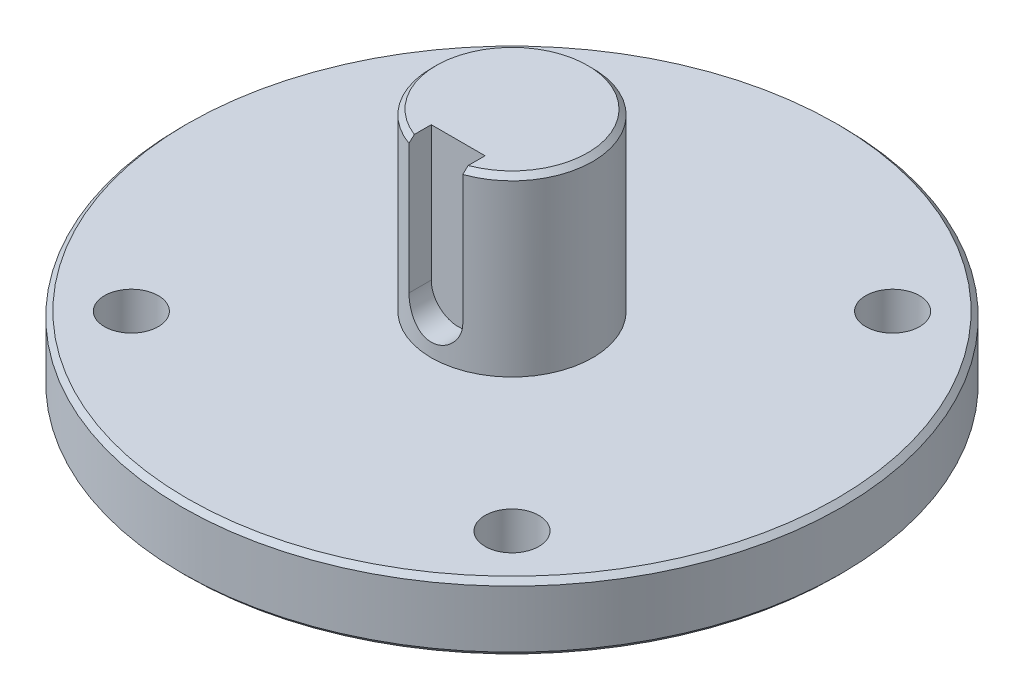
SolidWorks part; units mm, degrees
material "AISI 1045 Steel, cold drawn"
ref_plane "Front Plane" through (0, 0, 0) normal (0, 0, 1) x (1, 0, 0)
ref_plane "Top Plane" through (0, 0, 0) normal (0, 1, 0) x (1, 0, 0)
ref_plane "Right Plane" through (0, 0, 0) normal (1, 0, 0) x (0, 0, -1)
sketch "Sketch1" plane through (0, 0, 0) normal (0, 0, 1) x (1, 0, 0)
  line L0 (0, 0) -> (-49, 0)
  line L1 (-49, 0) -> (-49, 10)
  line L2 (-49, 10) -> (-12, 10)
  line L3 (-12, 10) -> (-12, 36)
  line L4 (-12, 36) -> (0, 36)
  line L5 (0, 36) -> (0, 0)
  dimension "D1" = 12
  dimension "D2" = 26
  dimension "D3" = 10
  dimension "D4" = 49
revolve "Revolve1" add sketch "Sketch1" angle 360 about L5
sketch "Sketch2" plane through (0, 10, 0) normal (0, 1, 0) x (1, 0, 0)
  line L1 (-28.2843, -28.2843) -> (28.2843, -28.2843) construction
  line L2 (-28.2843, -28.2843) -> (-28.2843, 28.2843) construction
  line L3 (-28.2843, 28.2843) -> (28.2843, 28.2843) construction
  line L4 (28.2843, -28.2843) -> (28.2843, 28.2843) construction
  line L5 (-28.2843, -28.2843) -> (28.2843, 28.2843) construction
  line L6 (-28.2843, 28.2843) -> (28.2843, -28.2843) construction
  circle A0 centre (-28.2843, 28.2843) radius 4
  circle A1 centre (28.2843, 28.2843) radius 4
  circle A2 centre (28.2843, -28.2843) radius 4
  circle A3 centre (-28.2843, -28.2843) radius 4
  point P0 (0, 0)
  dimension "D2" = 8
  dimension "D1" = 80
extrude "Cut-Extrude1" cut sketch "Sketch2" against normal up to next
ref_plane "Plane1" through (0, 0, 12) normal (0, 0, 1) x (1, 0, 0)
sketch "Sketch3" plane through (0, 0, 12) normal (0, 0, 1) x (1, 0, 0)
  line L0 (0, 36) -> (0, 10) construction
  line L1 (12, 36) -> (-12, 36) construction
  line L2 (49, 10) -> (-49, 10) construction
  line L3 (-4, 36) -> (4, 36)
  line L4 (4, 36) -> (4, 16)
  line L5 (-4, 36) -> (-4, 16)
  arc A0 (-4, 16) -> (4, 16) centre (0, 16) ccw
  point P9 (0, 36)
  dimension "D1" = 8
  dimension "D2" = 20
extrude "Cut-Extrude2" cut sketch "Sketch3" against normal blind 4
chamfer "Chamfer1" distance 0.75 angle 45 3 edges at (0, 0, 49) (0, 10, 49) (0, 36, -12)
ref_axis "Axis1" through (0, 0, 0) along (0, 1, 0)
sketch "Sketch4" plane through (0, 10, 0) normal (0, 1, 0) x (1, 0, 0)
  circle A0 centre (0, 0) radius 32.5
  dimension "D1" = 65
